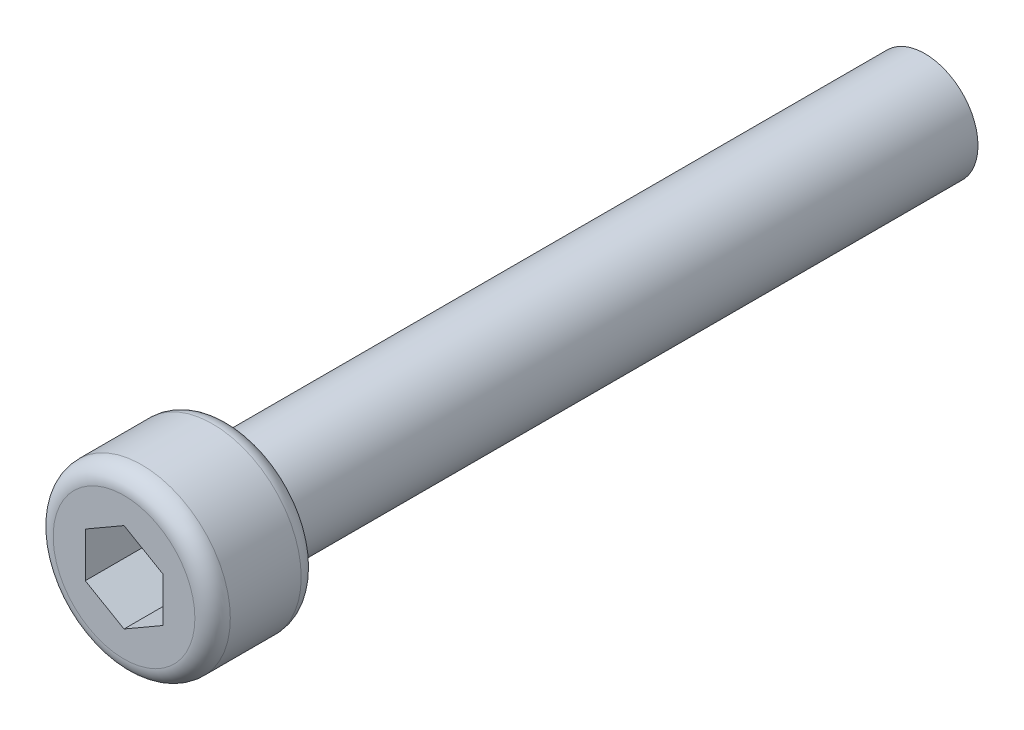
SolidWorks part; units mm, degrees
ref_plane "Front Plane" through (0, 0, 0) normal (0, 0, 1) x (1, 0, 0)
ref_plane "Top Plane" through (0, 0, 0) normal (0, 1, 0) x (1, 0, 0)
ref_plane "Right Plane" through (0, 0, 0) normal (1, 0, 0) x (0, 0, -1)
sketch "Sketch1" plane through (0, 0, 0) normal (0, 0, 1) x (1, 0, 0)
  circle A1 centre (0, 1.5842) radius 1.5
extrude "Boss-Extrude1" add sketch "Sketch1" against normal up to surface (19.6 mm away)
sketch "Sketch2" plane through (0, 0, 0) normal (0, 0, 1) x (1, 0, 0)
  circle A0 centre (0, 1.5842) radius 2.5
extrude "Boss-Extrude2" add sketch "Sketch2" along normal blind 3
fillet "Fillet1" radius 0.5 2 edges at (2.5, 1.5842, 3) (2.5, 1.5842, 0)
sketch "Sketch3" plane through (0, 0, 3) normal (0, 0, 1) x (1, 0, 0)
  line L1 (0, 0.3207) -> (1.0942, 0.9524)
  line L2 (1.0942, 0.9524) -> (1.0942, 2.2159)
  line L3 (1.0942, 2.2159) -> (0, 2.8477)
  line L4 (0, 2.8477) -> (-1.0942, 2.2159)
  line L5 (-1.0942, 2.2159) -> (-1.0942, 0.9524)
  line L6 (-1.0942, 0.9524) -> (0, 0.3207)
  circle A0 centre (0, 1.5842) radius 1.0942 construction
extrude "Cut-Extrude1" cut sketch "Sketch3" against normal blind 2
